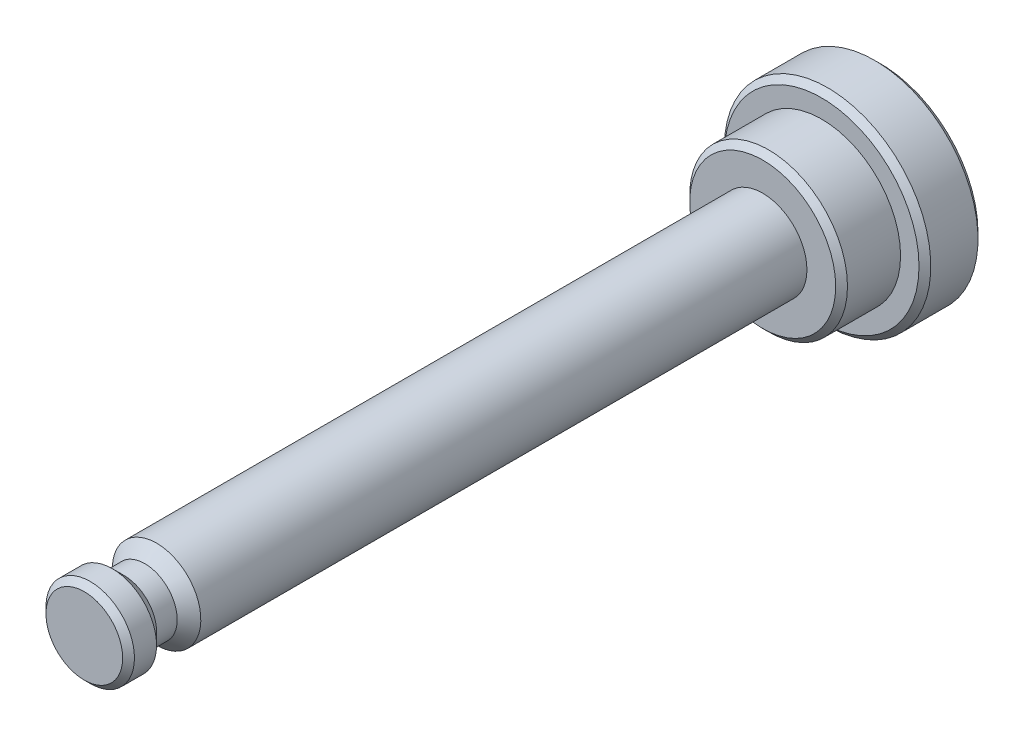
SolidWorks part; units mm, degrees
ref_plane "Front" through (0, 0, 0) normal (0, 0, 1) x (1, 0, 0)
ref_plane "Top" through (0, 0, 0) normal (0, 1, 0) x (1, 0, 0)
ref_plane "Right" through (0, 0, 0) normal (1, 0, 0) x (0, 0, -1)
sketch "Sketch1" plane through (0, 0, 0) normal (0, 0, 1) x (1, 0, 0)
  circle A0 centre (0, 0) radius 2.675
  dimension "D1" = 5.35
extrude "Countersink" add sketch "Sketch1" against normal blind 2
sketch "Sketch2" plane through (0, 0, 0) normal (0, 0, 1) x (1, 0, 0)
  circle A0 centre (0, 0) radius 1.5
  dimension "D1" = 3
extrude "Shaft" add sketch "Sketch2" along normal blind 23
sketch "Sketch3" plane through (0, 0, -2) normal (0, 0, -1) x (-1, 0, 0)
  circle A3 centre (0, 0) radius 3.5
  dimension "D1" = 7
extrude "Head" add sketch "Sketch3" along normal blind 2
sketch "Sketch4" plane through (0, 0, 0) normal (1, 0, 0) x (0, 0, -1)
  line L0 (0, 0) -> (-21.3, 0) construction
  line L1 (-21.3, 0) -> (-21.3, 4.3666) construction
  line L2 (-22.05, 1.5) -> (-20.55, 1.5)
  line L3 (0, 1.5) -> (-23, 1.5) construction
  line L6 (-20.55, 1.5) -> (-20.95, 1.1)
  line L7 (-20.95, 1.1) -> (-21.65, 1.1)
  line L8 (-21.65, 1.1) -> (-22.05, 1.5)
  dimension "D1" = 21.3
  dimension "D2" = 1.5
  dimension "D3" = 45
  dimension "D4" = 0.4
revolve "e-Clip Notch" cut sketch "Sketch4" angle 360 about L0
chamfer "Deburs" distance 0.2 angle 45 4 edges at (1.5, 0, 23) (-3.5, 0, -2) (-3.5, 0, -4) (2.675, 0, 0)
equation "\"D1@Sketch1\"=\"Hardware Head Countersink Diameter@Box Assy.Assembly\"-.25mm"
equation "\"D1@Shaft\"=\"Hardware Length@Box Assy.Assembly\"+3mm"
equation "\"D1@Sketch4\"=\"Hardware Length@Box Assy.Assembly\" + 1.3mm"
equation "\"D1@Sketch2\"=\"Hardware Clearance Hole Diameter@Box Assy.Assembly\"-.15"
